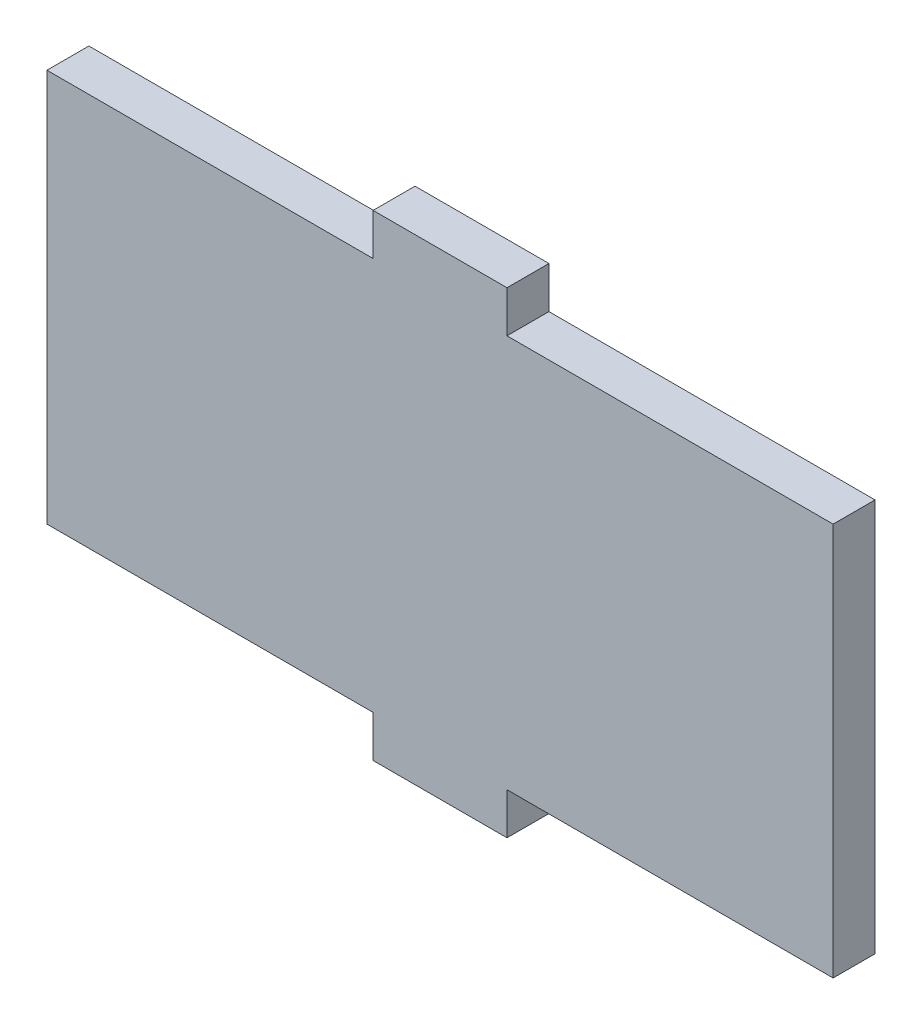
SolidWorks part; units mm, degrees
ref_plane "Front Plane" through (0, 0, 0) normal (0, 0, 1) x (1, 0, 0)
ref_plane "Top Plane" through (0, 0, 0) normal (0, 1, 0) x (1, 0, 0)
ref_plane "Right Plane" through (0, 0, 0) normal (1, 0, 0) x (0, 0, -1)
sketch "Sketch2" plane through (0, 0, 0) normal (0, 0, 1) x (1, 0, 0)
  line L1 (-32.5494, -8.3608) -> (27.4506, -8.3608)
  line L2 (-32.5494, -8.3608) -> (-32.5494, 51.6392)
  line L3 (-32.5494, 51.6392) -> (27.4506, 51.6392)
  line L4 (27.4506, -8.3608) -> (27.4506, 51.6392)
  dimension "D1" = 60
  dimension "D2" = 60
extrude "Top" [suppressed] add sketch "Sketch2" along normal blind 3.2
sketch "Sketch3" [suppressed] plane through (0, 0, 3.2) normal (0, 0, 1) x (1, 0, 0)
  line L0 (22.4506, 46.6392) -> (22.4506, 1.9043) construction
  line L4 (27.4506, 51.6392) -> (-32.5494, 51.6392) construction
  line L6 (27.4506, -8.3608) -> (27.4506, 51.6392) construction
  circle A0 centre (20.9506, -1.6608) radius 1.5
  circle A1 centre (22.4506, 46.6392) radius 1.5
  circle A2 centre (-29.8494, 13.6392) radius 1.5
  circle A3 centre (-29.8494, 41.5392) radius 1.5
  dimension "D1" = 3
  dimension "D2" = 48.3
  dimension "D7" = 5
  dimension "D3" = 27.9
  dimension "D4" = 5.1
  dimension "D5" = 50.8
  dimension "D6" = 5
extrude "Arduino Holes" [suppressed] cut sketch "Sketch3" against normal blind 3.2
sketch "Sketch5" [suppressed] plane through (0, 0, 0) normal (0, 0, -1) x (-1, 0, 0)
  line L0 (2.5494, -8.3608) -> (2.5494, 51.6392) construction
  line L1 (32.5494, -8.3608) -> (-27.4506, -8.3608) construction
  line L2 (-27.4506, 51.6392) -> (32.5494, 51.6392) construction
  circle A0 centre (2.5494, 6.6392) radius 2
  circle A1 centre (-11.2006, 28.1392) radius 2
  circle A2 centre (16.2994, 28.1392) radius 2
  dimension "D1" = 4
  dimension "D2" = 27.5
  dimension "D3" = 21.5
  dimension "D4" = 15
extrude "Battery Cut" [suppressed] cut sketch "Sketch5" against normal blind 3.2
sketch "Sketch7" [suppressed] plane through (0, 0, 0) normal (0, 0, -1) x (-1, 0, 0)
  line L0 (2.5494, -8.3608) -> (2.5494, 51.6392) construction
  line L1 (32.5494, -8.3608) -> (-27.4506, -8.3608) construction
  line L2 (-27.4506, 51.6392) -> (32.5494, 51.6392) construction
  line L4 (7.4394, 51.6392) -> (-2.3406, 51.6392)
  line L5 (7.4394, 51.6392) -> (7.4394, 48.4592)
  line L6 (7.4394, 48.4592) -> (-2.3406, 48.4592)
  line L7 (-2.3406, 51.6392) -> (-2.3406, 48.4592)
  line L8 (-2.3406, -8.3608) -> (7.4394, -8.3608)
  line L9 (-2.3406, -8.3608) -> (-2.3406, -5.1808)
  line L10 (-2.3406, -5.1808) -> (7.4394, -5.1808)
  line L11 (7.4394, -8.3608) -> (7.4394, -5.1808)
  dimension "D1" = 3.18
  dimension "D2" = 9.78
  dimension "D3" = 3.18
  dimension "D4" = 9.78
extrude "Friction Fit" [suppressed] cut sketch "Sketch7" against normal blind 10
sketch "Sketch4" plane through (0, 0, 0) normal (0, 0, 1) x (1, 0, 0)
  line L0 (0, 13.2972) -> (0, -11.8071) construction
  line L1 (30, -15) -> (-30, -15)
  line L2 (30, -15) -> (30, 15)
  line L3 (30, 15) -> (-30, 15)
  line L4 (-30, -15) -> (-30, 15)
  line L5 (17.7111, 0) -> (-18.0699, 0) construction
  dimension "D1" = 60
  dimension "D2" = 30
extrude "Side" add sketch "Sketch4" along normal blind 3.2
sketch "Sketch8" plane through (0, 15, 0) normal (0, 1, 0) x (1, 0, 0)
  line L0 (30, 0) -> (-30, 0) construction
  line L1 (5.11, 0) -> (-5.11, 0)
  line L2 (5.11, 0) -> (5.11, -3.2)
  line L3 (5.11, -3.2) -> (-5.11, -3.2)
  line L4 (-5.11, 0) -> (-5.11, -3.2)
  line L5 (30, -3.2) -> (-30, -3.2) construction
  line L6 (0, 0) -> (0, -3.2) construction
  dimension "D1" = 10.22
extrude "Friction Extrude" add sketch "Sketch8" along normal blind 3.18
mirror "Mirror" about plane through (0, 0, 0) normal (0, 1, 0) of "Friction Extrude"
equation "\"Kerf\"= .22"
